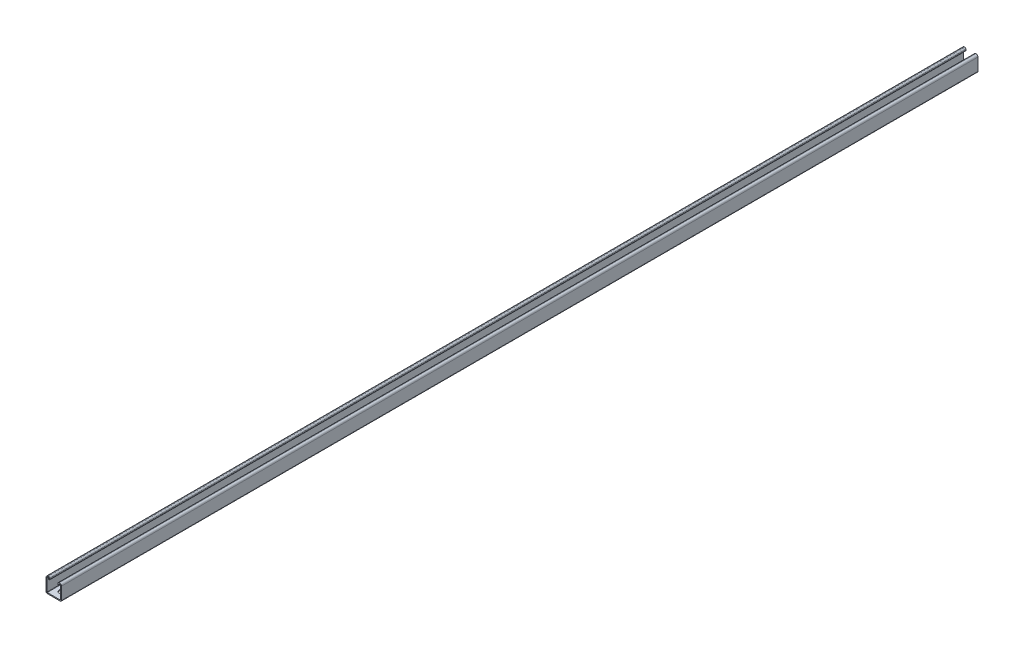
SolidWorks part; units mm, degrees
ref_plane "Front Plane" through (0, 0, 0) normal (0, 0, 1) x (1, 0, 0)
ref_plane "Top Plane" through (0, 0, 0) normal (0, 1, 0) x (1, 0, 0)
ref_plane "Right Plane" through (0, 0, 0) normal (1, 0, 0) x (0, 0, -1)
ref_plane "Plane1" through (0, 0, 3048) normal (0, 0, 1) x (1, 0, 0)
sketch "Sketch1" plane through (0, 0, 0) normal (0, 0, 1) x (1, 0, 0)
  line L0 (-20.6377, 0) -> (-17.9706, 0) construction
  line L1 (20.6377, 0) -> (17.9706, 0) construction
  line L2 (17.1769, -17.9704) -> (-17.1769, -17.9704)
  line L3 (-17.9706, -17.1766) -> (-17.9706, 15.5891)
  line L4 (-15.5894, 17.9704) -> (-14.5734, 17.9704)
  line L5 (-13.7797, 17.1766) -> (-13.7797, 14.8335)
  line L6 (-11.1127, 14.8335) -> (-11.1127, 17.1766)
  line L7 (-14.5734, 20.6374) -> (-15.5894, 20.6374)
  line L8 (-20.6377, 15.5891) -> (-20.6377, -17.1766)
  line L9 (-17.1769, -20.6374) -> (17.1769, -20.6374)
  line L10 (20.6377, 15.5891) -> (20.6377, -17.1766)
  line L11 (14.5734, 20.6374) -> (15.5894, 20.6374)
  line L12 (11.1127, 14.8335) -> (11.1127, 17.1766)
  line L13 (13.7797, 17.1766) -> (13.7797, 14.8335)
  line L14 (0, -17.9704) -> (0, -20.6374) construction
  line L15 (15.5894, 17.9704) -> (14.5734, 17.9704)
  line L16 (17.9706, -17.1766) -> (17.9706, 15.5891)
  arc A0 (-17.1769, -20.6374) -> (-20.6377, -17.1766) centre (-17.1769, -17.1766) cw
  arc A1 (-17.1769, -17.9704) -> (-17.9706, -17.1766) centre (-17.1769, -17.1766) cw
  arc A2 (-17.9706, 15.5891) -> (-15.5894, 17.9704) centre (-15.5894, 15.5891) cw
  arc A3 (-20.6377, 15.5891) -> (-15.5894, 20.6374) centre (-15.5894, 15.5891) cw
  arc A4 (-14.5734, 17.9704) -> (-13.7797, 17.1766) centre (-14.5734, 17.1766) cw
  arc A5 (-14.5734, 20.6374) -> (-11.1127, 17.1766) centre (-14.5734, 17.1766) cw
  arc A6 (-13.7797, 14.8335) -> (-11.1127, 14.8335) centre (-12.4462, 14.8335) ccw
  arc A7 (13.7797, 14.8335) -> (11.1127, 14.8335) centre (12.4462, 14.8335) cw
  arc A8 (14.5734, 20.6374) -> (11.1127, 17.1766) centre (14.5734, 17.1766) ccw
  arc A9 (14.5734, 17.9704) -> (13.7797, 17.1766) centre (14.5734, 17.1766) ccw
  arc A10 (20.6377, 15.5891) -> (15.5894, 20.6374) centre (15.5894, 15.5891) ccw
  arc A11 (17.9706, 15.5891) -> (15.5894, 17.9704) centre (15.5894, 15.5891) ccw
  arc A12 (17.1769, -17.9704) -> (17.9706, -17.1766) centre (17.1769, -17.1766) ccw
  arc A13 (17.1769, -20.6374) -> (20.6377, -17.1766) centre (17.1769, -17.1766) ccw
  dimension "D4" = 3.4608
  dimension "D5" = 5.0483
  dimension "D7" = 3.4608
  dimension "D1" = 34.3538
  dimension "D2" = 41.2748
  dimension "D3" = 2.667
  dimension "D6" = 1.016
  dimension "D8" = 2.3432
extrude "Primary Extrusion" add sketch "Sketch1" against normal blind 2438.4
sketch "Sketch58" plane through (0, -20.6374, 0) normal (0, 1, 0) x (-1, 0, 0)
  line L0 (7.1438, -29.3687) -> (7.1438, -21.4313)
  line L1 (-7.1438, -21.4313) -> (-7.1438, -29.3687)
  line L2 (0, 22.7012) -> (0, -22.7012) construction
  line L3 (-7.1438, -25.4) -> (7.1438, -25.4) construction
  line L4 (17.1769, 0) -> (-17.1769, 0) construction
  arc A0 (7.1438, -29.3687) -> (-7.1438, -29.3687) centre (0, -29.3687) cw
  arc A1 (-7.1438, -21.4313) -> (7.1438, -21.4313) centre (0, -21.4313) cw
  point P12 (0, -36.5125)
  point P13 (0, -14.2875)
  dimension "D2" = 22.225
  dimension "D1" = 14.2875
  dimension "D3" = 25.4
extrude "Slot Cut" cut sketch "Sketch58" along normal up to next contours L0 A1 L1 A0
pattern_linear "LPattern1" count 48 spacing 50.8 along (0, 0, -1) of "Slot Cut"
